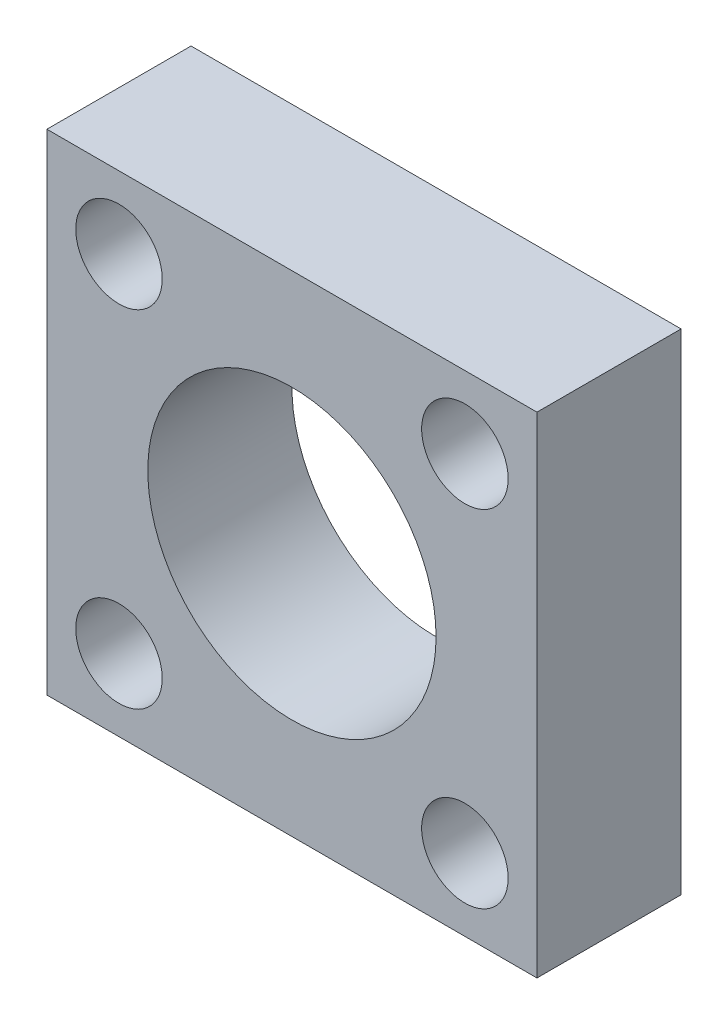
SolidWorks part; units mm, degrees
ref_plane "Front Plane" through (0, 0, 0) normal (0, 0, 1) x (1, 0, 0)
ref_plane "Top Plane" through (0, 0, 0) normal (0, 1, 0) x (1, 0, 0)
ref_plane "Right Plane" through (0, 0, 0) normal (1, 0, 0) x (0, 0, -1)
sketch "Sketch1" plane through (0, 0, 0) normal (0, 0, 1) x (1, 0, 0)
  line L1 (-18.4444, 12.1111) -> (15.5556, 12.1111)
  line L2 (-18.4444, 12.1111) -> (-18.4444, -21.8889)
  line L3 (-18.4444, -21.8889) -> (15.5556, -21.8889)
  line L4 (15.5556, 12.1111) -> (15.5556, -21.8889)
  circle A0 centre (-1.4444, -4.8889) radius 10
  dimension "D3" = 17
  dimension "D1" = 34
  dimension "D2" = 34
  dimension "D4" = 17
extrude "Boss-Extrude1" add sketch "Sketch1" along normal blind 10
sketch "Sketch2" plane through (0, 0, 10) normal (0, 0, 1) x (1, 0, 0)
  line L0 (-18.4444, 12.1111) -> (-18.4444, -21.8889) construction
  line L1 (15.5556, 12.1111) -> (-18.4444, 12.1111) construction
  circle A0 centre (-13.4444, 7.1111) radius 3
  dimension "D1" = 5
  dimension "D2" = 5
extrude "Cut-Extrude1" cut sketch "Sketch2" against normal blind 5
pattern_linear "LPattern1" count 2 spacing 24 along (1, 0, 0) count 2 spacing 24 along (0, -1, 0) of "Cut-Extrude1"
